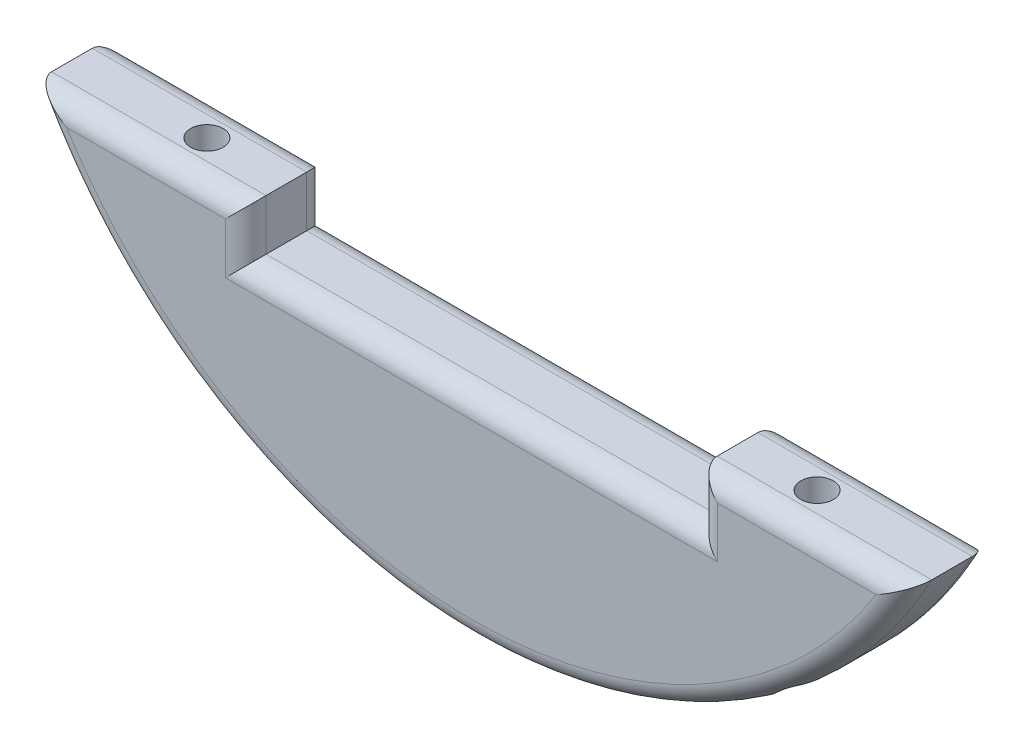
SolidWorks part; units mm, degrees
material "Pure Lead"
ref_plane "Front Plane" through (0, 0, 0) normal (0, 0, 1) x (1, 0, 0)
ref_plane "Top Plane" through (0, 0, 0) normal (0, 1, 0) x (1, 0, 0)
ref_plane "Right Plane" through (0, 0, 0) normal (1, 0, 0) x (0, 0, -1)
sketch "Sketch1" plane through (0, 0, 0) normal (0, 0, 1) x (1, 0, 0)
  line L0 (-46.6476, -15) -> (46.6476, -15)
  line L1 (-43.2666, -23) -> (43.2666, -23)
  line L2 (-33.9411, -28) -> (33.9411, -28)
  line L3 (-22.1811, -38) -> (-22.1811, -23)
  line L4 (-29.9539, -23) -> (-37.51, -23)
  line L5 (22.1811, -38) -> (22.1811, -23)
  line L6 (-22.1811, -38) -> (22.1811, -38)
  circle A0 centre (0, 0) radius 49
  circle A1 centre (0, 0) radius 44
  dimension "D1" = 8
  dimension "D2" = 98
  dimension "D3" = 88
  dimension "D4" = 15
  dimension "D5" = 5
  dimension "D8" = 10
extrude "Boss-Extrude1" add sketch "Sketch1" along normal blind 8 contours L1 A1 L2 L3 | A1 L1 A0 | L2 A1 L3 | L5 A1 L2 | L2 A1 L1 L5 | L3 L6 L5 L2 | L6 A1
sketch "Sketch2" plane through (0, -23, 0) normal (0, 1, 0) x (1, 0, 0)
  line L0 (-43.2666, -8) -> (-43.2666, 0) construction
  line L1 (-14.3, 0) -> (14.3, 0) construction
  circle A1 centre (-29.9966, -4) radius 1.6
  dimension "D1" = 4
  dimension "D4" = 13.27
extrude "Cut-Extrude1" cut sketch "Sketch2" against normal through all
sketch "Sketch3" plane through (0, -23, 0) normal (0, 1, 0) x (1, 0, 0)
  circle A1 centre (-29.9966, -4) radius 3.05
extrude "Cut-Extrude2" cut sketch "Sketch3" along normal up to surface (20 mm away) from offset 25
mirror "Mirror1" about plane through (0, 0, 0) normal (1, 0, 0) of "Cut-Extrude2", "Cut-Extrude1"
fillet "Fillet1" radius 2 12 edges at (0, -28, 8) (0, -28, 0) (22.1811, -25.5, 0) (-22.1811, -25.5, 8) (-32.7238, -23, 8) (0, -49, 8) (32.7238, -23, 8) (22.1811, -25.5, 8) (32.7238, -23, 0) (0, -49, 0) (-32.7238, -23, 0) (-22.1811, -25.5, 0)
